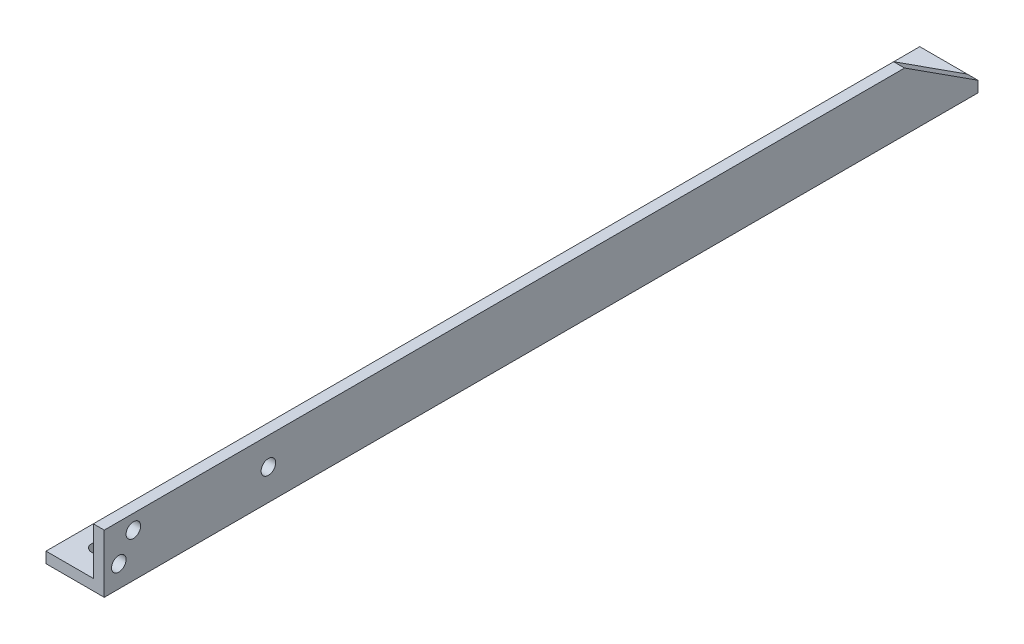
SolidWorks part; units mm, degrees
material "6061 Alloy"
ref_plane "Front Plane" through (0, 0, 0) normal (0, 0, 1) x (1, 0, 0)
ref_plane "Top Plane" through (0, 0, 0) normal (0, 1, 0) x (1, 0, 0)
ref_plane "Right Plane" through (0, 0, 0) normal (1, 0, 0) x (0, 0, -1)
sketch "Sketch1" plane through (0, 0, 0) normal (0, 0, 1) x (1, 0, 0)
  line L0 (0, 0) -> (0, -25.4)
  line L1 (0, -25.4) -> (-25.4, -25.4)
  line L2 (-25.4, -25.4) -> (-25.4, -20.6375)
  line L3 (-25.4, -20.6375) -> (-4.7625, -20.6375)
  line L4 (-4.7625, -20.6375) -> (-4.7625, 0)
  line L5 (-4.7625, 0) -> (0, 0)
  dimension "D1" = 4.7625
  dimension "D2" = 4.7625
  dimension "D3" = 25.4
  dimension "D4" = 25.4
extrude "Boss-Extrude1" add sketch "Sketch1" along normal blind 381
sketch "Sketch9" plane through (-4.7625, 0, 0) normal (-1, 0, 0) x (0, 0, 1)
  line L0 (0, -20.6375) -> (32.0266, 0)
  line L1 (381, 0) -> (0, 0) construction
  dimension "D1" = 38.1
extrude "Cut-Extrude2" cut sketch "Sketch9" against normal through all and the other way through all
sketch "Sketch10" plane through (-4.7625, 0, 0) normal (-1, 0, 0) x (0, 0, 1)
  line L0 (381, 0) -> (32.0266, 0) construction
  line L1 (381, 0) -> (381, -20.6375) construction
  circle A0 centre (374.65, -15.875) radius 3.175
  circle A1 centre (368.3, -6.35) radius 3.175
  dimension "D1" = 6.35
  dimension "D2" = 6.35
  dimension "D3" = 15.875
  dimension "D4" = 6.35
  dimension "D5" = 6.35
  dimension "D6" = 12.7
extrude "Cut-Extrude3" cut sketch "Sketch10" against normal up to next
sketch "Sketch11" plane through (0, 0, 0) normal (1, 0, 0) x (0, 0, -1)
  circle A0 centre (-309.4303, -11.9296) radius 3.175 construction
  circle A1 centre (-309.4303, -11.9296) radius 3.175
extrude "Cut-Extrude4" cut sketch "Sketch11" against normal up to next
sketch "Sketch12" plane through (0, -20.6375, 0) normal (0, 1, 0) x (1, 0, 0)
  line L0 (-25.4, -381) -> (-25.4, 0) construction
  line L1 (-4.7625, -381) -> (-25.4, -381) construction
  circle A0 centre (-15.0812, -368.3) radius 3.175
  dimension "D1" = 6.35
  dimension "D2" = 10.3187
  dimension "D3" = 12.7
extrude "Cut-Extrude5" cut sketch "Sketch12" against normal up to next
